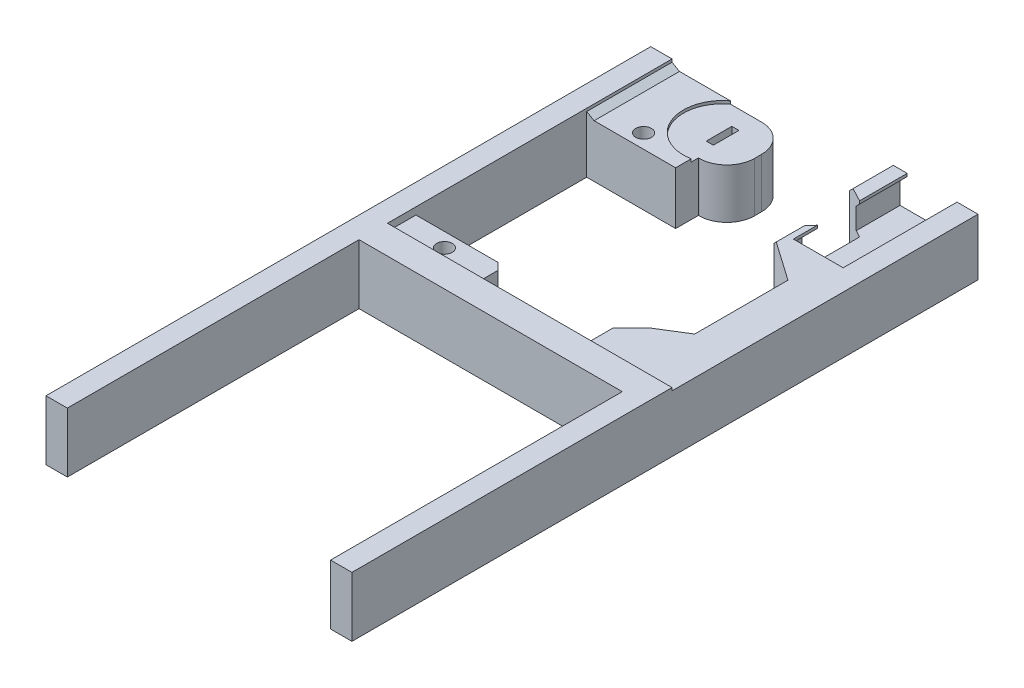
SolidWorks part; units mm, degrees
ref_plane "Front Plane" through (0, 0, 0) normal (0, 0, 1) x (1, 0, 0)
ref_plane "Top Plane" through (0, 0, 0) normal (0, 1, 0) x (1, 0, 0)
ref_plane "Right Plane" through (0, 0, 0) normal (1, 0, 0) x (0, 0, -1)
sketch "Sketch1" plane through (0, 0, 0) normal (0, 1, 0) x (1, 0, 0)
  line L0 (0, 0) -> (0, 59.6401) construction
  line L1 (-18.5, -19.2885) -> (-21.5, -19.2885)
  line L2 (18.5, 17.7115) -> (21.5, 17.7115)
  line L3 (18.5, 17.7115) -> (18.5, 65.7115)
  line L4 (18.5, 65.7115) -> (21.5, 65.7115)
  line L5 (21.5, 17.7115) -> (21.5, 65.7115)
  line L6 (18.5, 17.7115) -> (21.5, 17.7115)
  line L7 (18.5, 17.7115) -> (18.5, -19.2885)
  line L8 (18.5, -19.2885) -> (21.5, -19.2885)
  line L9 (21.5, 17.7115) -> (21.5, -19.2885)
  line L10 (-21.5, 17.7115) -> (-21.5, -19.2885)
  line L11 (-18.5, 17.7115) -> (-21.5, 17.7115)
  line L12 (-18.5, 17.7115) -> (-18.5, -19.2885)
  line L13 (-18.5, 65.7115) -> (-21.5, 65.7115)
  line L14 (-21.5, 17.7115) -> (-21.5, 65.7115)
  line L15 (-18.5, 17.7115) -> (-21.5, 17.7115)
  line L16 (-18.5, 17.7115) -> (-18.5, 65.7115)
  dimension "18" = 18.5
  dimension "D2" = 3
  dimension "D3" = 37
  dimension "D4" = 48
extrude "Boss-Extrude1" add sketch "Sketch1" against normal blind 8 contours L12 L11 L10 L1 | L11 L16 L13 L14 | L9 L2 L7 L8 | L2 L5 L4 L3 region at (-20, 0, 0.7885) region at (-20, 0, -41.7115) region at (20, 0, -41.7115) region at (20, 0, 0.7885)
sketch "Sketch2" plane through (21.5, 0, 0) normal (1, 0, 0) x (0, 0, -1)
  line L0 (-19.2885, -4) -> (65.7115, -4) construction
  line L1 (-19.2885, -8) -> (-19.2885, 0) construction
  line L2 (65.7115, -8) -> (65.7115, 0) construction
  line L3 (65.7115, -8) -> (-19.2885, -8) construction
  line L4 (17.7115, 0) -> (17.7115, -8) construction
  line L5 (65.7115, 0) -> (-19.2885, 0) construction
  circle A0 centre (11.7115, -4) radius 1.5
  circle A2 centre (-8.2885, -4) radius 1.5
  circle A3 centre (1.7115, -4) radius 1.5 [skipped]
  dimension "D2" = 3
  dimension "D1" = 4
  dimension "D3" = 37
  dimension "D4" = 6
  dimension "D5" = 3
extrude "Cut-Extrude1" [suppressed] cut sketch "Sketch2" against normal through all both and the other way through all
chamfer "Chamfer1" [suppressed] distance 1 angle 48
chamfer "Chamfer2" [suppressed] distance 1 angle 48
sketch "Sketch4" plane through (0, -8, 0) normal (0, -1, 0) x (1, 0, 0)
  line L0 (-21.5, -65.7115) -> (-21.5, 19.2885) construction
  line L1 (-2, -65.7115) -> (-21.5, -65.7115)
  line L2 (-2, -65.7115) -> (-2, -56.9115)
  line L3 (-2, -56.9115) -> (-21.5, -56.9115)
  line L4 (-21.5, -65.7115) -> (-21.5, -56.9115)
  line L10 (-18.5, -65.7115) -> (-18.5, 19.2885) construction
  line L13 (-18.5, -65.7115) -> (-21.5, -65.7115) construction
  dimension "D1" = 8.8
  dimension "D2" = 16.5
extrude "Boss-Extrude3" add sketch "Sketch4" against normal blind 6.6
sketch "Sketch3" plane through (0, -8, 0) normal (0, -1, 0) x (1, 0, 0)
  line L0 (-21.5, -65.7115) -> (-21.5, 19.2885) construction
  line L1 (-21.5, -57.7115) -> (-6, -57.7115)
  line L2 (-21.5, -57.7115) -> (-21.5, -53.7115)
  line L3 (-21.5, -53.7115) -> (-6, -53.7115)
  line L4 (-6, -57.7115) -> (-6, -53.7115)
  line L6 (0, 0) -> (0, -31.4212) construction
  line L13 (-2, -65.7115) -> (-21.5, -65.7115) construction
  line L14 (-21.5, -41.7115) -> (-3.8096, -41.7115) construction
  line L15 (-21.5, -29.7115) -> (-6, -29.7115)
  line L16 (-6, -25.7115) -> (-6, -29.7115)
  line L17 (-21.5, -25.7115) -> (-6, -25.7115)
  line L18 (-21.5, -25.7115) -> (-21.5, -29.7115)
  line L19 (-18.5, -56.9115) -> (-18.5, 19.2885) construction
  circle A0 centre (-12.5, -55.7115) radius 1.04
  circle A2 centre (-12.5, -27.7115) radius 1.04
  dimension "D4" = 2
  dimension "D5" = 2.08
  dimension "D1" = 14
  dimension "D2" = 10
  dimension "D3" = 4
  dimension "D6" = 6
  dimension "D7" = 15.5
extrude "Servo Holder" add sketch "Sketch3" along normal blind 0.4 and the other way offset from surface 1 other way up to plane "Top Plane"
sketch "Sketch5" plane through (0, 0, 0) normal (0, 1, 0) x (1, 0, 0)
  line L0 (-2, 61.3115) -> (-21.5, 61.3115) construction
  line L1 (-2, 65.7115) -> (-2, 56.9115) construction
  line L2 (-21.5, 65.7115) -> (-21.5, -19.2885) construction
  line L4 (-6.5, 63.1115) -> (-7.5, 63.1115)
  line L5 (-6.5, 63.1115) -> (-6.5, 59.5115)
  line L6 (-6.5, 59.5115) -> (-7.5, 59.5115)
  line L7 (-7.5, 63.1115) -> (-7.5, 59.5115)
  line L8 (-6.5, 63.1115) -> (-7.5, 59.5115) construction
  line L9 (-6.5, 59.5115) -> (-7.5, 63.1115) construction
  circle A0 centre (-12.5, 55.7115) radius 1.04 construction
  point P6 (-7, 61.3115)
  dimension "D3" = 5.5
  dimension "D1" = 1
  dimension "D2" = 3.6
extrude "Cut-Extrude2" cut sketch "Sketch5" against normal through all
sketch "Sketch6" plane through (0, -1.4, 0) normal (0, 1, 0) x (1, 0, 0)
  line L0 (-6.5, 61.3115) -> (-7.5, 61.3115) construction
  line L1 (-6.5, 59.5115) -> (-6.5, 63.1115) construction
  line L2 (-7.5, 63.1115) -> (-7.5, 59.5115) construction
  circle A0 centre (-7, 61.3115) radius 5.25
  dimension "D1" = 10.5
extrude "Brass" [suppressed] add sketch "Sketch6" along normal blind 2.6
fillet "Fillet1" [suppressed] radius 2.6
sketch "Sketch11" plane through (0, -8, 0) normal (0, -1, 0) x (1, 0, 0)
  line L0 (21.5, -65.7115) -> (21.5, 19.2885) construction
  line L1 (-21.5, -25.7115) -> (21.5, -25.7115)
  line L2 (-21.5, -25.7115) -> (-21.5, -21.7115)
  line L3 (-21.5, -21.7115) -> (21.5, -21.7115)
  line L4 (21.5, -25.7115) -> (21.5, -21.7115)
  dimension "D1" = 4
extrude "Boss-Extrude9" add sketch "Sketch11" against normal blind 8 and the other way up to surface (0.4 mm away) other way up to face at (-13.75, -8.4, -55.7115)
sketch "Sketch14" plane through (0, -8, 0) normal (0, -1, 0) x (1, 0, 0)
  line L1 (18.5, -25.7115) -> (30.7236, -25.7115)
  line L2 (18.5, -25.7115) -> (18.5, -70.6911)
  line L3 (18.5, -70.6911) -> (30.7236, -70.6911)
  line L4 (30.7236, -25.7115) -> (30.7236, -70.6911)
extrude "Cut-Extrude5" cut sketch "Sketch14" against normal blind 10
fillet "Fillet2" radius 3.9 2 edges at (-2, -4.7, -65.7115) (-2, -4.7, -56.9115)
sketch "Sketch13" plane through (0, -8.4, 0) normal (0, -1, 0) x (-1, 0, 0)
  circle A0 centre (12.5, 55.7115) radius 1.1
  circle A1 centre (12.5, 27.7115) radius 1.1
  dimension "D1" = 2.2
extrude "Cut-Extrude4" cut sketch "Sketch13" against normal through all both and the other way through all
sketch "Sketch17" plane through (0, 0, -25.7115) normal (0, 0, -1) x (-1, 0, 0)
  line L0 (-21.5, -8.4) -> (6, -8.4) construction
  line L1 (-8.6, -8.4) -> (-21.5, -8.4)
  line L2 (-8.6, -8.4) -> (-8.6, -0.4)
  line L3 (-8.6, -0.4) -> (-21.5, -0.4)
  line L4 (-21.5, -8.4) -> (-21.5, -0.4)
  line L5 (-21.5, -8.4) -> (-21.5, 0) construction
  dimension "D1" = 12.9
  dimension "D2" = 8
extrude "Boss-Extrude11" add sketch "Sketch17" along normal blind 27
sketch "Sketch16" plane through (0, 0, -52.7115) normal (0, 0, -1) x (-1, 0, 0)
  line L0 (-18.55, -2) -> (-18.55, -0.4)
  line L1 (-10.55, -4.8) -> (-19.75, -4.8)
  line L2 (-10.55, -4.8) -> (-10.55, -2)
  line L3 (-10.55, -2) -> (-19.75, -2)
  line L4 (-19.75, -4.8) -> (-19.75, -2)
  line L5 (-18.55, -0.4) -> (-21.5, -0.4)
  line L6 (-21.5, -0.4) -> (-21.5, -8.4)
  line L7 (-21.5, -8.4) -> (-8.6, -8.4)
  line L8 (-15.05, -4.3136) -> (-15.05, -1.3136) construction
  line L9 (-8.6, -8.4) -> (6, -8.4) construction
  line L10 (-8.6, -0.4) -> (-8.6, -8.4)
  line L11 (-11.55, -2) -> (-11.55, -0.4)
  line L12 (-11.55, -0.4) -> (-8.6, -0.4)
  line L13 (-21.5, -0.4) -> (-21.5, 0) construction
  line M30 (-8.6, -8.4) -> (-8.6, -0.4)
  line M31 (-8.6, -0.4) -> (-21.5, -0.4)
  line M32 (-21.5, -0.4) -> (-21.5, -8.4)
  line M33 (-21.5, -8.4) -> (-8.6, -8.4)
  dimension "D1" = 2.8
  dimension "D2" = 9.2
  dimension "D3" = 1.6
  dimension "D4" = 1.75
  dimension "D5" = 3.6
  dimension "D6" = 3.5
  dimension "D7" = 1.95
extrude "Boss-Extrude12" add sketch "Sketch16" along normal offset from surface (16 mm away) 3 contours L11 L3 L2 L1 L4 L0 M31 M32 M33 M30 region at (15.0111, -5.33, -52.7115) up to face at (-15.3, -3.1333, -65.7115) offset beyond the face yes
sketch "Sketch18" plane through (0, -8, 0) normal (0, -1, 0) x (1, 0, 0)
  line L0 (18.5, 19.2885) -> (21.5, 19.2885) construction
  line L1 (-21.5, -65.7115) -> (-5.9, -65.7115)
  line L2 (-21.5, -65.7115) -> (-21.5, -52.3785)
  line L5 (-21.5, -57.7115) -> (-18.5, -57.7115)
  line L6 (-21.5, -57.7115) -> (-21.5, 19.2885)
  line L7 (-21.5, 19.2885) -> (-18.5, 19.2885)
  line L8 (-18.5, -57.7115) -> (-18.5, 19.2885)
  line L9 (21.5, 19.2885) -> (18.5, 19.2885)
  line L10 (21.5, 19.2885) -> (21.5, -21.7115)
  line L11 (21.5, -21.7115) -> (18.5, -21.7115)
  line L12 (18.5, 19.2885) -> (18.5, -21.7115)
  line L13 (-18.5, 19.2885) -> (-21.5, 19.2885) construction
  line L14 (21.5, -21.7115) -> (21.5, 19.2885) construction
  line L15 (-18.5, -53.7115) -> (-18.5, -29.7115) construction
  line L16 (-2, -61.8115) -> (-2, -60.8115) construction
  arc A0 (-5.9, -56.9115) -> (-2, -60.8115) centre (-5.9, -60.8115) cw
  arc A1 (-5.9, -65.7115) -> (-2, -61.8115) centre (-5.9, -61.8115) ccw
  arc A5 (-2, -60.8115) -> (-5.9, -56.9115) centre (-5.9, -60.8115) ccw construction
  arc A6 (-5.9, -65.7115) -> (-2, -61.8115) centre (-5.9, -61.8115) ccw construction
  line M7 (-6.5, -63.1115) -> (-7.5, -63.1115)
  line M8 (-7.5, -63.1115) -> (-7.5, -59.5115)
  line M9 (-7.5, -59.5115) -> (-6.5, -59.5115)
  line M10 (-6.5, -59.5115) -> (-6.5, -63.1115)
  line M11 (-21.5, -65.7115) -> (-5.9, -65.7115)
  line M13 (-2, -61.8115) -> (-2, -60.8115)
  line M15 (-5.9, -56.9115) -> (-6, -56.9115)
  line M16 (-6, -56.9115) -> (-6, -57.7115)
  line M17 (-6, -57.7115) -> (-21.5, -57.7115)
  line M18 (-21.5, -57.7115) -> (-21.5, -65.7115)
extrude "Boss-Extrude13" add sketch "Sketch18" along normal up to surface (0.4 mm away) contours A1 A0 M11 M13 M15 M16 M17 M18 M10 M7 M8 M9 | L8 L7 L6 | L9 L12 L11 L10 | L6 L5 L8 L7 region at (-12.0872, -8, -61.6443) region at (-20, -8, -19.2115) region at (20, -8, -1.2115) up to face at (-12.5, -8.4, -26.6115)
chamfer "Chamfer14" distance 1.2 angle 45 2 edges at (18.55, -2, -60.7115) (11.55, -2, -60.7115)
sketch "Sketch20" plane through (0, -0.4, 0) normal (0, 1, 0) x (1, 0, 0)
  line L0 (11.55, 62.0219) -> (2.5155, 66.7653)
  line L1 (11.55, 68.7115) -> (11.55, 52.7115) construction
  line L2 (2.5155, 66.7653) -> (1.9978, 58.6591)
  line L3 (1.9978, 58.6591) -> (1.9978, 45.1224)
  line L4 (1.9978, 45.1224) -> (11.55, 56.0872)
  line L5 (11.55, 56.0872) -> (11.55, 62.0219)
  line L6 (8.6, 25.7115) -> (21.5, 25.7115) construction
  line L7 (9.7, 25.7115) -> (1.9978, 25.7115)
  line L8 (9.7, 25.7115) -> (9.7, 53.9636)
  line L9 (9.7, 53.9636) -> (1.9978, 53.9636)
  line L10 (1.9978, 25.7115) -> (1.9978, 53.9636)
  line L11 (21.5, 68.7115) -> (21.5, 25.7115) construction
  line L12 (16.1748, 47.3223) -> (4.9747, 55.1624)
  line L13 (4.9747, 55.1624) -> (4.9747, 27.2638)
  line L14 (4.9747, 27.2638) -> (16.1748, 34.2118)
  line L15 (16.1748, 34.2118) -> (16.1748, 47.3223)
  line M6 (8.6, 25.7115) -> (21.5, 25.7115)
  line M11 (11.55, 52.7115) -> (11.55, 68.7115)
  line M13 (8.6, 68.7115) -> (8.6, 25.7115)
  dimension "D1" = 11.8
extrude "Cut-Extrude6" cut sketch "Sketch20" against normal through all both and the other way through all contours L13 L12 L9 L0 L2 L3 M13 | L12 L9 M13 | L12 L4 L9 M13 | L12 L8 L4 | L14 L8 L12 L4 M13 | L14 L15 L12 L8 | L13 L14 L4 M13 | L9 L13 L4 L12 M13 | L12 L13 L9 | L9 L4 L0 M11 M13 | L4 L12 M13 | L14 L8 M13 M6 region at (9.9584, -0.4, -58.6946) region at (5.2143, -0.4, -59.6186) region at (7.9616, -0.4, -53.5183) region at (8.9667, -0.4, -53.5427) region at (9.3205, -0.4, -52.8242) region at (6.2284, -0.4, -51.906) region at (5.5455, -0.4, -54.3632) region at (12.6721, -0.4, -40.9066) region at (9.1441, -0.4, -41.0471) region at (6.8133, -0.4, -39.527) region at (9.1651, -0.4, -27.7874)
chamfer "Chamfer19" [suppressed] distance 0.7 angle 33
ref_plane "Plane1" through (0, 20.6, 0) normal (0, 1, 0) x (1, 0, 0)
sketch "Sketch22" plane through (0, 20.6, 0) normal (0, 1, 0) x (1, 0, 0)
  line L0 (0, 17.7115) -> (0, -19.2885) construction
  line L1 (-21.5, -19.2885) -> (21.5, -19.2885)
  line L2 (-21.5, -19.2885) -> (-21.5, 17.7115)
  line L3 (-21.5, 17.7115) -> (21.5, 17.7115)
  line L4 (21.5, -19.2885) -> (21.5, 17.7115)
  line L5 (-18.5, 21.7115) -> (-18.5, -19.2885) construction
  line L6 (18.5, 21.7115) -> (18.5, -19.2885) construction
  line L7 (-21.5, -19.2885) -> (-21.5, 65.7115) construction
  line L9 (-18.5, -19.2885) -> (-21.5, -19.2885) construction
  circle A0 centre (0, 10.7115) radius 2.7
  circle A2 centre (8, -9.2885) radius 2.7
  circle A3 centre (-8, -9.2885) radius 2.7
  dimension "D3" = 7
  dimension "D4" = 10
  dimension "D6" = 5.4
  dimension "D1" = 37
  dimension "D5" = 8
extrude "Mount Top" [suppressed] add sketch "Sketch22" against normal blind 4 separate body
sketch "Sketch23" [suppressed] plane through (-21.5, 0, 0) normal (-1, 0, 0) x (0, 0, 1)
  line L0 (19.2885, 16.6) -> (19.2885, 20.6) construction
  line L1 (19.2885, 20.6) -> (-17.7115, 20.6)
  line L2 (19.2885, 20.6) -> (19.2885, -8.4)
  line L3 (19.2885, -8.4) -> (-17.7115, -8.4)
  line L4 (-17.7115, 20.6) -> (-17.7115, -8.4)
  line L5 (-65.7115, -8.4) -> (19.2885, -8.4) construction
  line L6 (-17.7115, 20.6) -> (19.2885, 20.6) construction
extrude "Mount Side1" [suppressed] add sketch "Sketch23" against normal up to surface (3 mm away)
sketch "Sketch24" [suppressed] plane through (21.5, 0, 0) normal (1, 0, 0) x (0, 0, -1)
  line L0 (-19.2885, -8.4) -> (68.7115, -8.4) construction
  line L1 (-19.2885, 20.6) -> (17.7115, 20.6)
  line L2 (-19.2885, 20.6) -> (-19.2885, -8.4)
  line L3 (-19.2885, -8.4) -> (17.7115, -8.4)
  line L4 (17.7115, 20.6) -> (17.7115, -8.4)
extrude "Mount Side2" [suppressed] add sketch "Sketch24" against normal up to surface (3 mm away)
chamfer "Chamfer20" [suppressed] distance 25.8 angle 40
sketch "Sketch29" plane through (0, -1.4, 0) normal (0, 1, 0) x (1, 0, 0)
  line L0 (-18.5, 57.7115) -> (-6, 57.7115) construction
  line L1 (-18.5, 65.7115) -> (-9.6141, 65.7115)
  line L2 (-18.5, 65.7115) -> (-18.5, 57.7115)
  line L3 (-18.5, 57.7115) -> (-9.6141, 57.7115)
  line L4 (-9.6141, 65.7115) -> (-9.6141, 57.7115)
extrude "Boss-Extrude20" add sketch "Sketch29" along normal up to surface (0.4 mm away) up to face at (-12.5, -1, -54.6115)
sketch "Sketch25" [suppressed] plane through (0, 0, -17.7115) normal (0, 0, -1) x (-1, 0, 0)
  line L0 (21.5, 20.6) -> (21.5, 0) construction
  line L1 (-21.5, -0.4) -> (21.5, -0.4)
  line L2 (-21.5, -0.4) -> (-21.5, 0.5976)
  line L3 (-21.5, 0.5976) -> (21.5, 0.5976)
  line L4 (21.5, -0.4) -> (21.5, 0.5976)
  line L6 (18.5, -1) -> (0, -1)
  line L7 (18.5, -1) -> (18.5, -1.6016)
  line L8 (18.5, -1.6016) -> (0, -1.6016)
  line L9 (0, -1) -> (0, -1.6016)
extrude "Cut-Extrude7" [suppressed] cut sketch "Sketch25" along normal through all
chamfer "Chamfer22" [suppressed] distance 2 angle 45
chamfer "Chamfer23" distance 1 angle 45 1 edges at (9.7, -0.4, -52.9091)
chamfer "Chamfer24" distance 1 angle 45 3 edges at (8.6, -0.4, -66.1411) (-6, -4.7, -29.7115) (9.7, -4.4, -30.1952) first distance on face at (8.6, -4.4, -66.1411) first distance on face at (-6, -4.7, -27.7115) first distance on face at (9.7, -4.4, -27.9534)
sketch "Sketch26" plane through (0, -1.4, 0) normal (0, 1, 0) x (1, 0, 0)
  line L0 (-7.5, 63.1115) -> (-6.5, 63.1115) construction
  line L1 (-7.5, 59.5115) -> (-7.5, 63.1115) construction
  circle A0 centre (-7, 61.3115) radius 5.5
  dimension "D1" = 11
  dimension "D2" = 1.8
  dimension "D3" = 0.5
extrude "Cut-Extrude8" cut sketch "Sketch26" along normal blind 10
chamfer "Chamfer25" distance 0.6 angle 60 1 edges at (-18.5, -1, -59.7115) first distance on face at (-18.5, -2.6, -43.7115)
